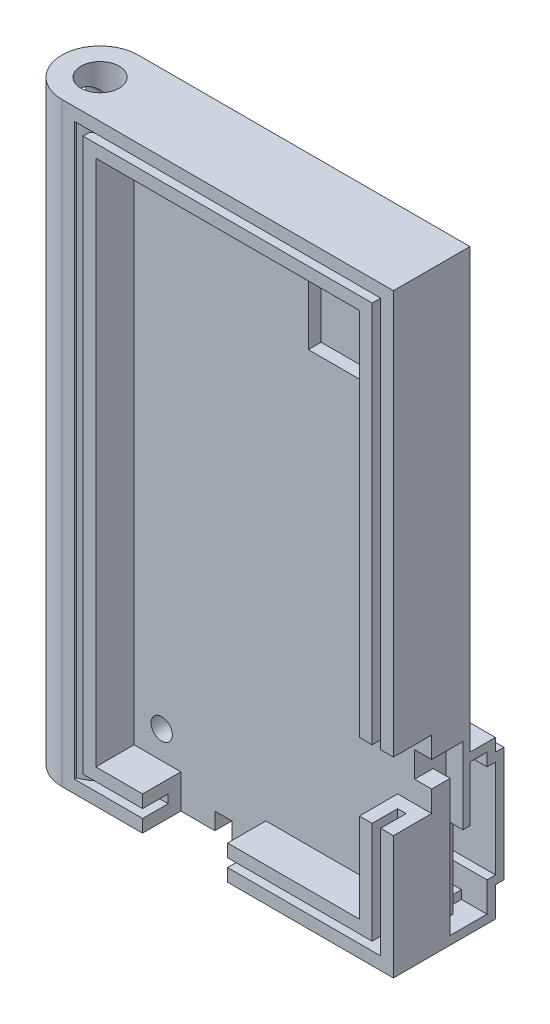
SolidWorks part; units mm, degrees
ref_plane "Front Plane" through (0, 0, 0) normal (0, 0, 1) x (1, 0, 0)
ref_plane "Top Plane" through (0, 0, 0) normal (0, 1, 0) x (1, 0, 0)
ref_plane "Right Plane" through (0, 0, 0) normal (1, 0, 0) x (0, 0, -1)
sketch "Sketch1" plane through (0, 0, 0) normal (0, 0, 1) x (1, 0, 0)
  line L1 (0, 0) -> (39, 0)
  line L2 (0, 0) -> (0, 70)
  line L3 (0, 70) -> (39, 70)
  line L4 (39, 0) -> (39, 70)
  dimension "D1" = 70
  dimension "D2" = 39
extrude "Base" add sketch "Sketch1" along normal blind 4.5
sketch "Sketch2" plane through (0, 0, 4.5) normal (0, 0, 1) x (1, 0, 0)
  line L0 (0, 70) -> (0, 0) construction
  line L1 (39, 70) -> (0, 70)
  line L2 (39, 70) -> (39, 66)
  line L3 (39, 66) -> (0, 66)
  line L4 (0, 70) -> (0, 66)
  line L5 (0, 0) -> (39, 0) construction
  line L6 (0, 66) -> (4, 66)
  line L7 (0, 66) -> (0, 0)
  line L8 (0, 0) -> (4, 0)
  line L9 (4, 66) -> (4, 0)
  line L10 (39, 0) -> (39, 70) construction
  line L11 (4, 0) -> (39, 0)
  line L12 (4, 0) -> (4, 4)
  line L13 (4, 4) -> (39, 4)
  line L14 (39, 0) -> (39, 4)
  line L16 (39, 66) -> (35, 66)
  line L17 (39, 66) -> (39, 4)
  line L18 (39, 4) -> (35, 4)
  line L19 (35, 66) -> (35, 4)
  line M6 (0, 70) -> (0, 0)
  line M7 (0, 0) -> (39, 0)
  line M8 (39, 0) -> (39, 70)
  line M9 (39, 70) -> (0, 70)
  dimension "D1" = 4
  dimension "D2" = 4
  dimension "D3" = 4
  dimension "D4" = 4
extrude "Walls" add sketch "Sketch2" along normal blind 4.5 contours L3 M8 M9 M6 | L3 L19 L13 M8 | L9 L3 M6 M7 | L13 L9 M7 M8 region at (19.5, 68, 4.5) region at (37, 35, 4.5) region at (2, 33, 4.5) region at (21.5, 2, 4.5)
sketch "Sketch3" plane through (0, 4, 0) normal (0, 1, 0) x (1, 0, 0)
  line L0 (4, -4.5) -> (35, -4.5) construction
  line L1 (9.5, -4.5) -> (19.5, -4.5)
  line L2 (9.5, -4.5) -> (9.5, -9)
  line L3 (9.5, -9) -> (19.5, -9)
  line L4 (19.5, -4.5) -> (19.5, -9)
  line L5 (4, -9) -> (35, -9) construction
  line L6 (4, -9) -> (4, -4.5) construction
  dimension "D1" = 5.5
  dimension "D2" = 15.5
extrude "PWR connector hole" cut sketch "Sketch3" against normal blind 4
sketch "Sketch4" plane through (35, 0, 0) normal (-1, 0, 0) x (0, 0, 1)
  line L0 (4.5, 66) -> (4.5, 4) construction
  line L1 (4.5, 14.5) -> (9, 14.5)
  line L2 (4.5, 14.5) -> (4.5, 22.5)
  line L3 (4.5, 22.5) -> (9, 22.5)
  line L4 (9, 14.5) -> (9, 22.5)
  line L5 (9, 66) -> (9, 4) construction
  line L6 (9, 4) -> (4.5, 4) construction
  dimension "D1" = 10.5
  dimension "D2" = 18.5
extrude "GPS connector hole" cut sketch "Sketch4" against normal blind 4
sketch "Sketch5" plane through (0, 0, 4.5) normal (0, 0, 1) x (1, 0, 0)
  line L0 (4, 4) -> (9.5, 4) construction
  line L1 (4, 66) -> (4, 4) construction
  line L2 (19.5, 66) -> (19.5, 4) construction
  line L3 (35, 66) -> (4, 66) construction
  line L5 (19.5, 35) -> (4, 35) construction
  line L6 (4, 66) -> (4, 4) construction
  circle A0 centre (7.25, 7.25) radius 1.25
  circle A1 centre (31.75, 7.25) radius 1.25
  circle A2 centre (7.25, 62.75) radius 1.25
  dimension "D1" = 3.25
  dimension "D3" = 2.5
  dimension "D2" = 3.25
extrude "Mounting holes" cut sketch "Sketch5" against normal blind 4
sketch "Sketch22" plane through (0, 0, 4.5) normal (0, 0, 1) x (1, 0, 0)
  line L1 (35, 66) -> (24.5, 66)
  line L2 (35, 66) -> (35, 54.5)
  line L3 (35, 54.5) -> (24.5, 54.5)
  line L4 (24.5, 66) -> (24.5, 54.5)
  dimension "D1" = 10.5
  dimension "D2" = 11.5
extrude "Antenna space" cut sketch "Sketch22" against normal blind 1.5
sketch "Sketch7" plane through (0, 0, 0) normal (0, 0, -1) x (-1, 0, 0)
  line L0 (-39, 0) -> (-39, 18.5) construction
  line L1 (-39, 0) -> (-39, 70) construction
  line L3 (-39, 1) -> (-8, 1)
  line L4 (-39, 1) -> (-39, 17.5)
  line L5 (-39, 17.5) -> (-8, 17.5)
  line L6 (-8, 1) -> (-8, 17.5)
  line L9 (0, 0) -> (-39, 0) construction
  line L10 (-39, 0) -> (-7, 0)
  line L11 (-7, 0) -> (-7, 18.5)
  line L12 (-7, 18.5) -> (-39, 18.5)
  line L13 (-39, 18.5) -> (-39, 17.5)
  line L14 (-39, 1) -> (-39, 0)
  line M8 (-39, 70) -> (-39, 0)
  line M9 (-39, 0) -> (0, 0)
  dimension "D1" = 18.5
  dimension "D2" = 1
  dimension "D3" = 16.5
  dimension "D4" = 31
  dimension "D5" = 32
  dimension "D6" = 18.5
extrude "GPS mount" add sketch "Sketch7" along normal blind 3 contours L11 L12 L5 L6 L3 M8 M9 region at (23.5, 0.6304, 0)
sketch "Sketch8" plane through (8, 0, 0) normal (1, 0, 0) x (0, 0, -1)
  line L0 (3, 17.5) -> (0, 17.5) construction
  line L1 (1, 17.5) -> (2, 17.5)
  line L2 (1, 17.5) -> (1, 16.5)
  line L3 (1, 16.5) -> (2, 16.5)
  line L4 (2, 17.5) -> (2, 16.5)
  line L5 (0, 1) -> (0, 17.5) construction
  line L6 (0, 9.25) -> (3, 9.25) construction
  line L7 (3, 1) -> (3, 17.5) construction
  line L8 (1, 2) -> (2, 2)
  line L9 (2, 1) -> (2, 2)
  line L10 (1, 1) -> (2, 1)
  line L11 (1, 1) -> (1, 2)
  dimension "D1" = 1
  dimension "D2" = 1
  dimension "D3" = 1
extrude "GPS rails" add sketch "Sketch8" along normal blind 28
sketch "Sketch9" plane through (8, 0, 0) normal (1, 0, 0) x (0, 0, -1)
  line L1 (3, 1) -> (2, 1)
  line L2 (3, 1) -> (3, 17.5)
  line L3 (3, 17.5) -> (2, 17.5)
  line L4 (2, 1) -> (2, 17.5)
extrude "GPS \"roof\"" add sketch "Sketch9" along normal blind 14
sketch "Sketch10" plane through (22, 0, 0) normal (1, 0, 0) x (0, 0, -1)
  line L0 (3, 1) -> (3, 17.5) construction
  line L1 (2, 17.5) -> (3, 17.5)
  line L2 (2, 17.5) -> (2, 16)
  line L3 (2, 16) -> (3, 16)
  line L4 (3, 17.5) -> (3, 16)
  line L6 (2, 1) -> (3, 1)
  line L7 (2, 1) -> (2, 4.5)
  line L8 (2, 4.5) -> (3, 4.5)
  line L9 (3, 1) -> (3, 4.5)
  dimension "D1" = 1.5
  dimension "D2" = 3.5
extrude "GPS \"roof" add sketch "Sketch10" along normal blind 17
sketch "Sketch18" plane through (0, 0, -3) normal (0, 0, -1) x (-1, 0, 0)
  line L0 (-22, 4.5) -> (-22, 16) construction
  line L1 (-39, 4.5) -> (-21, 4.5)
  line L2 (-39, 4.5) -> (-39, 3.5)
  line L3 (-39, 3.5) -> (-21, 3.5)
  line L4 (-21, 4.5) -> (-21, 3.5)
  dimension "D1" = 1
  dimension "D2" = 1
extrude "Chip roof1" add sketch "Sketch18" along normal blind 1
sketch "Sketch19" plane through (0, 4.5, 0) normal (0, 1, 0) x (1, 0, 0)
  line L0 (39, 4) -> (39, 2) construction
  line L1 (21, 4) -> (39, 4)
  line L2 (21, 4) -> (21, 3)
  line L3 (21, 3) -> (39, 3)
  line L4 (39, 4) -> (39, 3)
extrude "Chip roof2" add sketch "Sketch19" along normal blind 12.5
sketch "Sketch11" plane through (0, 0, 0) normal (0, 0, -1) x (-1, 0, 0)
  line L0 (0, 0) -> (-7, 0) construction
  line L1 (-4, 0) -> (-5, 0)
  line L2 (-4, 0) -> (-4, 21.5)
  line L3 (-4, 21.5) -> (-5, 21.5)
  line L4 (-5, 0) -> (-5, 21.5)
  line L5 (-7, 0) -> (-7, 18.5) construction
  line L7 (0, 70) -> (0, 0) construction
  line L8 (-5, 21.5) -> (-22, 21.5)
  line L9 (-5, 21.5) -> (-5, 20.5)
  line L10 (-5, 20.5) -> (-22, 20.5)
  line L11 (-22, 21.5) -> (-22, 20.5)
  line L12 (-7, 18.5) -> (-39, 18.5) construction
  line L13 (-28, 18.5) -> (-27, 18.5)
  line L14 (-28, 18.5) -> (-28, 21.5)
  line L15 (-28, 21.5) -> (-27, 21.5)
  line L16 (-27, 18.5) -> (-27, 21.5)
  line M5 (-7, 0) -> (0, 0)
  line M9 (-39, 18.5) -> (-7, 18.5)
  dimension "D1" = 1
  dimension "D2" = 2
  dimension "D3" = 21.5
  dimension "D4" = 1
  dimension "D5" = 22
  dimension "D6" = 5
  dimension "D7" = 1
  dimension "D8" = 3
extrude "PWR cable holder1" add sketch "Sketch11" along normal blind 3 contours L4 L2 L3 M5 | L8 L11 L10 L4 | L16 L15 L14 M9 region at (4.5, 10.75, 0) region at (13.5, 21, 0) region at (27.5, 20, 0)
sketch "Sketch12" plane through (0, 0, 0) normal (0, -1, 0) x (1, 0, 0)
  line L0 (19.5, 4.5) -> (9.5, 4.5) construction
  line L1 (5, 0) -> (15.5, 0)
  line L2 (5, 0) -> (5, 2)
  line L3 (5, 2) -> (15.5, 2)
  line L4 (15.5, 0) -> (15.5, 2)
  line L5 (9.5, 4.5) -> (9.5, 9) construction
  line L6 (13.5, 4.5) -> (15.5, 4.5)
  line L7 (13.5, 4.5) -> (13.5, 2)
  line L8 (13.5, 2) -> (15.5, 2)
  line L9 (15.5, 4.5) -> (15.5, 2)
  line L10 (19.5, 9) -> (19.5, 4.5) construction
  line M5 (19.5, 4.5) -> (9.5, 4.5)
  line M13 (5, 0) -> (7, 0)
  dimension "D1" = 2
  dimension "D2" = 4
  dimension "D3" = 4
  dimension "D4" = 0
extrude "PWR cable holder2" cut sketch "Sketch12" against normal blind 2 contours L1 L4 L3 L2 M13 | L9 L7 L3 M5 region at (10.25, 0, 1) region at (14.5, 0, 3.25)
sketch "Sketch13" plane through (39, 0, 0) normal (1, 0, 0) x (0, 0, -1)
  line L0 (-4.5, 22.5) -> (-4.5, 14.5) construction
  line L1 (-4.5, 20) -> (-2.3266, 20)
  line L2 (-4.5, 20) -> (-4.5, 17)
  line L3 (-4.5, 17) -> (-2.3266, 17)
  line L4 (-2.3266, 20) -> (-2.3266, 17)
  line L5 (-9, 22.5) -> (-4.5, 22.5) construction
  line L6 (-4.5, 14.5) -> (-9, 14.5) construction
  line L7 (-2.3266, 17) -> (-2.3266, 11)
  line L8 (0, 1) -> (-2.3266, 1)
  line L9 (0, 1) -> (0, 11)
  line L10 (0, 11) -> (-2.3266, 11)
  line L11 (-2.3266, 1) -> (-2.3266, 11)
  line L18 (-2.3266, 11) -> (-0.8266, 11)
  line L19 (-2.3266, 11) -> (-2.3266, 20)
  line L20 (-2.3266, 20) -> (-0.8266, 20)
  line L21 (-0.8266, 11) -> (-0.8266, 20)
  line M19 (-4.5, 22.5) -> (-4.5, 14.5)
  line M27 (0, 1) -> (0, 17.5)
  dimension "D1" = 2.5
  dimension "D2" = 2.5
  dimension "D3" = 10
  dimension "D4" = 1.5
  dimension "D5" = 2.3266
extrude "GPS cable holder" cut sketch "Sketch13" against normal blind 2 contours L4 L1 L3 M19 | L10 L21 L20 L4 L7 | L11 L8 L10 M27 region at (39, 18.5, 3.4133) region at (39, 15.5, 1.5766) region at (39, 6, 1.1633)
sketch "Sketch14" plane through (0, 0, 9) normal (0, 0, 1) x (1, 0, 0)
  line L1 (1.5, 1.5) -> (2.5, 1.5)
  line L2 (1.5, 1.5) -> (1.5, 68.5)
  line L3 (1.5, 68.5) -> (2.5, 68.5)
  line L4 (2.5, 1.5) -> (2.5, 68.5)
  line L5 (0, 70) -> (0, 0) construction
  line L6 (4, 66) -> (4, 4) construction
  line L7 (39, 70) -> (0, 70) construction
  line L8 (35, 66) -> (4, 66) construction
  line L9 (2.5, 68.5) -> (37.5, 68.5)
  line L10 (2.5, 68.5) -> (2.5, 67.5)
  line L11 (2.5, 67.5) -> (37.5, 67.5)
  line L12 (37.5, 68.5) -> (37.5, 67.5)
  line L13 (39, 22.5) -> (39, 70) construction
  line L14 (19.5, 70) -> (19.5, 0) construction
  line L15 (0, 35) -> (39, 35) construction
  line L16 (37.5, 68.5) -> (36.5, 68.5)
  line L17 (36.5, 1.5) -> (36.5, 68.5)
  line L18 (37.5, 1.5) -> (36.5, 1.5)
  line L19 (37.5, 1.5) -> (37.5, 68.5)
  line L20 (2.5, 2.5) -> (37.5, 2.5)
  line L21 (37.5, 1.5) -> (37.5, 2.5)
  line L22 (2.5, 1.5) -> (37.5, 1.5)
  line L23 (2.5, 1.5) -> (2.5, 2.5)
  line M15 (35, 22.5) -> (39, 22.5)
  line M20 (9.5, 0) -> (9.5, 4)
  dimension "D2" = 1.5
  dimension "D3" = 1.5
  dimension "D4" = 1.5
  dimension "D5" = 1.5
extrude "Lid mount" cut sketch "Sketch14" against normal blind 3 contours L1 L4 L3 L2 | L4 L22 L20 M20 | L22 L17 L20 M20 | L20 L17 L18 L19 | L17 L20 L19 M15 | L19 L11 L17 M15 | L11 L17 L9 L4 | L17 L11 L12 L9 region at (2, 35, 9) region at (6, 2, 9) region at (23, 2, 9) region at (19.5, 68, 9) region at (37, 2, 9) region at (37, 68, 9) region at (37, 45, 9) region at (37, 12.5, 9)
sketch "Sketch15" plane through (0, 0, 0) normal (0, -1, 0) x (1, 0, 0)
  line L0 (0, 9) -> (0, 0) construction
  circle A0 centre (0, 4.5) radius 4.5
extrude "Ballon mount" add sketch "Sketch15" against normal blind 70
sketch "Sketch16" plane through (0, 0, 0) normal (0, -1, 0) x (1, 0, 0)
  line L0 (0, 0) -> (0, 4.5) construction
  circle A0 centre (0, 4.5) radius 2.25
  dimension "D1" = 4.5
extrude "Balloon mount hole" cut sketch "Sketch16" against normal blind 70
sketch "Sketch17" plane through (0, 0, 9) normal (0, 0, 1) x (1, 0, 0)
  line L0 (35, 66) -> (4, 66) construction
  line L1 (4, 4) -> (6, 4)
  line L2 (4, 4) -> (4, 66)
  line L3 (4, 66) -> (6, 66)
  line L4 (6, 4) -> (6, 66)
  dimension "D1" = 2
extrude "Correction" cut sketch "Sketch17" against normal blind 4.5
ref_plane "Plane1" through (-4.5, 0, 0) normal (-1, 0, 0) x (0, 0, 1)
sketch "Sketch21" plane through (-4.5, 0, 0) normal (-1, 0, 0) x (0, 0, 1)
  line L0 (4.5, 0) -> (4.5, 4.5) construction
  line L1 (0, 0) -> (9, 0) construction
  line L2 (0, 35) -> (9, 35) construction
  line L3 (0, 70) -> (0, 0) construction
  line L4 (9, 70) -> (9, 0) construction
  circle A0 centre (4.5, 4.5) radius 2.25
  circle A1 centre (4.5, 65.5) radius 2.25
  dimension "D2" = 4.5
  dimension "D1" = 4.5
extrude "Safety mount" cut sketch "Sketch21" against normal blind 4.5
